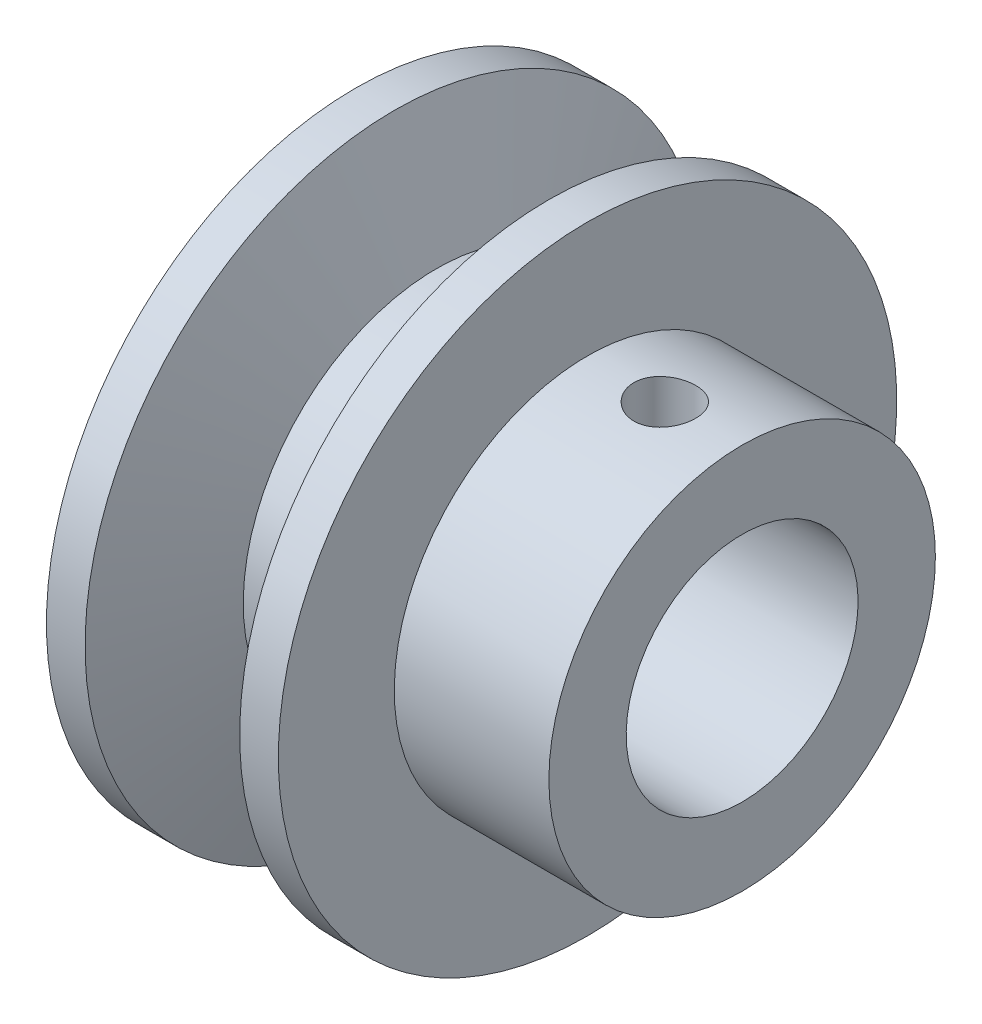
SolidWorks part; units mm, degrees
ref_plane "Front Plane" through (0, 0, 0) normal (0, 0, 1) x (1, 0, 0)
ref_plane "Top Plane" through (0, 0, 0) normal (0, 1, 0) x (1, 0, 0)
ref_plane "Right Plane" through (0, 0, 0) normal (1, 0, 0) x (0, 0, -1)
sketch "Sketch1" plane through (0, 0, 0) normal (0, 0, 1) x (1, 0, 0)
  line L0 (0, 0) -> (0, 40)
  line L1 (0, 40) -> (5, 40)
  line L2 (15, 50.9717) -> (15, -50.9717) construction
  line L3 (0, 0) -> (30, 0)
  line L4 (5, 40) -> (10.4596, 25)
  line L5 (25, 40) -> (30, 40)
  line L6 (30, 40) -> (30, 0)
  line L7 (10.4596, 25) -> (19.5404, 25)
  line L8 (25, 40) -> (19.5404, 25)
  point P6 (15, 0)
  point P13 (15, 25)
  dimension "D1" = 30
  dimension "D2" = 25
  dimension "D3" = 40
  dimension "D4" = 5
  dimension "D5" = 20
revolve "Revolve1" add sketch "Sketch1" angle 360 about L3
sketch "Sketch2" plane through (0, 0, 0) normal (-1, 0, 0) x (0, 0, 1)
  circle A0 centre (0, 0) radius 12.5
  dimension "D1" = 25
extrude "Cut-Extrude1" cut sketch "Sketch2" against normal through all
sketch "Sketch3" plane through (30, 0, 0) normal (1, 0, 0) x (0, 0, -1)
  circle A0 centre (0, 0) radius 25
  dimension "D1" = 50
extrude "Boss-Extrude1" add sketch "Sketch3" along normal blind 20
extrude "Cut-Extrude2" cut sketch "Sketch2<2>" against normal through all
sketch "Sketch2<2>" plane through (0, 0, 0) normal (-1, 0, 0) x (0, 0, 1) same geometry as "Sketch2"
sketch "Sketch5" plane through (0, 0, 0) normal (-1, 0, 0) x (0, 0, 1)
  circle A0 centre (0, 0) radius 20
  dimension "D1" = 40
extrude "Cut-Extrude3" cut sketch "Sketch5" against normal blind 5 draft 45
sketch "Sketch6" plane through (5, 0, 0) normal (-1, 0, 0) x (0, 0, 1)
  circle A0 centre (0, 0) radius 15
  dimension "D1" = 30
extrude "Cut-Extrude4" cut sketch "Sketch6" against normal through all
ref_plane "Plane1" through (0, 25, 0) normal (0, 1, 0) x (1, 0, 0)
sketch "Sketch10" plane through (0, 25, 0) normal (0, 1, 0) x (1, 0, 0)
  line L0 (30, -25) -> (30, 25) construction
  line L1 (30, -25) -> (50, -25) construction
  circle A0 centre (40, 0) radius 4
  dimension "D1" = 8
  dimension "D2" = 10
  dimension "D3" = 25
extrude "Cut-Extrude5" cut sketch "Sketch10" against normal up to next
